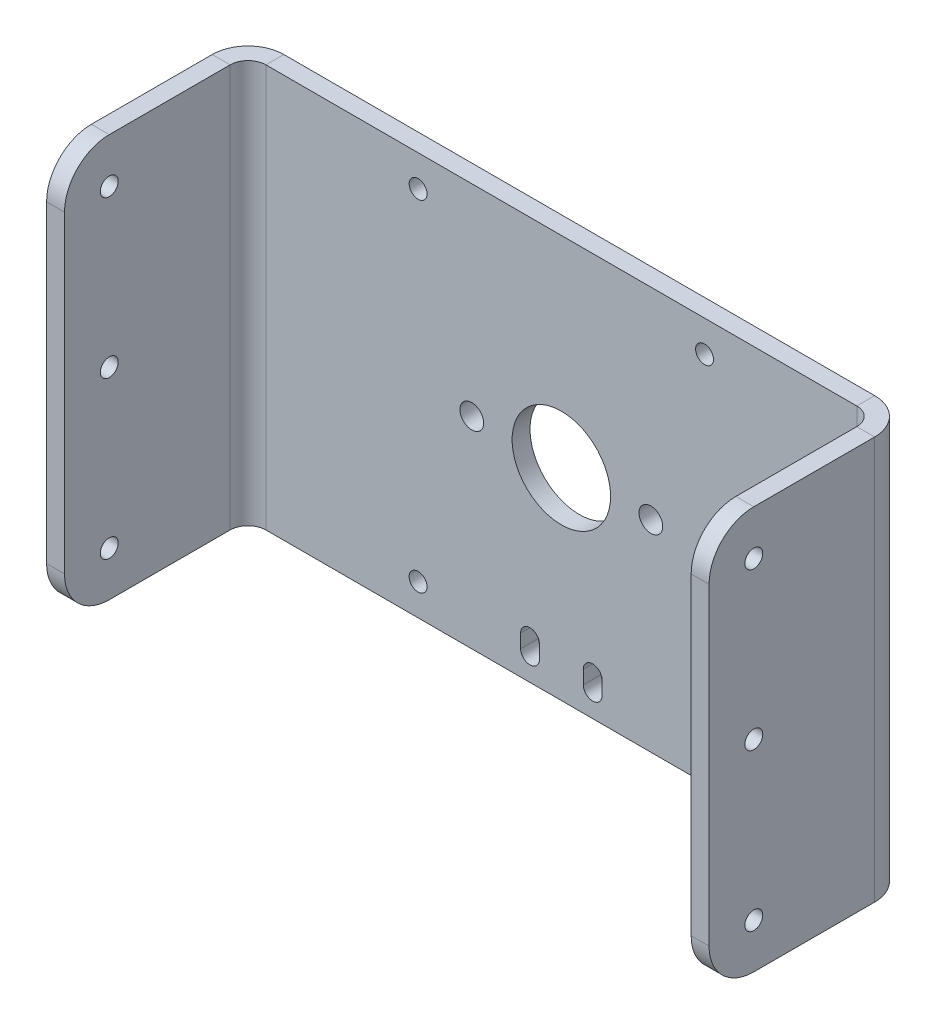
SolidWorks part; units mm, degrees
note: The reader was unsure of these and kept them because the rebuilt part matched: thickness of "Базовая кромка1", "Ребро-кромка1", "Листовой металл3", "Листовой металл4", "Листовой металл5", "Листовой металл7"; flange length of "Ребро-кромка1".
ref_plane "Спереди" through (0, 0, 0) normal (0, 0, 1) x (1, 0, 0)
ref_plane "Сверху" through (0, 0, 0) normal (0, 1, 0) x (1, 0, 0)
ref_plane "Справа" through (0, 0, 0) normal (1, 0, 0) x (0, 0, -1)
sketch "Эскиз1" plane through (0, 0, 0) normal (0, 0, 1) x (1, 0, 0)
  line L1 (-74, -45) -> (74, -45)
  line L2 (-74, -45) -> (-74, 45)
  line L3 (-74, 45) -> (74, 45)
  line L4 (74, -45) -> (74, 45)
  line L5 (-74, -45) -> (74, 45) construction
  line L6 (-74, 45) -> (74, -45) construction
  line L13 (-7, -36.5) -> (-7, -39.5) construction
  line L14 (-4.9, -36.5) -> (-4.9, -39.5)
  line L15 (-9.1, -36.5) -> (-9.1, -39.5)
  line L16 (7, -36.5) -> (7, -39.5) construction
  line L17 (9.1, -36.5) -> (9.1, -39.5)
  line L18 (4.9, -36.5) -> (4.9, -39.5)
  circle A0 centre (0, 0) radius 11
  circle A1 centre (20, 0) radius 2.65
  circle A2 centre (-20, 0) radius 2.65
  arc A12 (-4.9, -36.5) -> (-9.1, -36.5) centre (-7, -36.5) ccw
  arc A13 (-9.1, -39.5) -> (-4.9, -39.5) centre (-7, -39.5) ccw
  arc A14 (9.1, -36.5) -> (4.9, -36.5) centre (7, -36.5) ccw
  arc A15 (4.9, -39.5) -> (9.1, -39.5) centre (7, -39.5) ccw
  point P0 (0, 0)
  point P31 (-7, -38)
  point P36 (7, -38)
  dimension "D3" = 22
  dimension "D4" = 5.3
  dimension "D13" = 2.1
  dimension "D1" = 90
  dimension "D2" = 148
  dimension "D5" = 20
  dimension "D6" = 20
  dimension "D14" = 14
  dimension "D15" = 7
  dimension "D16" = 7
  dimension "D17" = 3
base flange "Базовая кромка1" sketch "Эскиз1" thickness 4 reverse thickness direction no parameters "D1"=0.7366
edge flange "Ребро-кромка1" sketch "Эскиз10" flange profiles "Эскиз10", "Эскиз11" flange angle 90 flange length 45 flange position material inside bend radius 4 thickness 4 relief rectangular parameters "D6"=10, "D8"=1
sketch "Эскиз10" plane through (-74, 0, 0) normal (-1, 0, 0) x (0, -1, 0)
  line L2 (-45, 0) -> (-45, 41)
  line L3 (-45, 41) -> (45, 41)
  line L4 (45, 41) -> (45, 0)
  line L7 (-45, 0) -> (45, 0) construction
  line L8 (-45, 0) -> (45, 0)
sketch "Эскиз11" plane through (74, 0, 0) normal (1, 0, 0) x (0, 1, 0)
  line L0 (-45, 0) -> (45, 0) construction
  line L1 (-45, 0) -> (45, 0)
  line L2 (-45, 0) -> (-45, 41)
  line L3 (-45, 41) -> (45, 41)
  line L4 (45, 41) -> (45, 0)
bend "EdgeBend1" bend radius 4 bend angle 90 parameters "D5"=1
bend "EdgeBend2" bend radius 4 bend angle 90 parameters "D5"=2
sketch "Эскиз12" plane through (74, 0, 0) normal (1, 0, 0) x (0, 0, -1)
  line L11 (-41, 45) -> (-41, -45) construction
  circle A0 centre (-31, 35) radius 2
  circle A1 centre (-31, -35) radius 2
  circle A2 centre (-31, 0) radius 2
  dimension "D1" = 4
  dimension "D2" = 35
  dimension "D3" = 35
  dimension "D4" = 10
extrude "Вырез-Вытянуть1" cut sketch "Эскиз12" against normal through all normal cut yes
fillet "Скругление1" radius 10 4 edges at (-72, 45, 41) (-72, -45, 41) (72, -45, 41) (72, 45, 41)
sketch "Эскиз13" plane through (0, 0, 0) normal (0, 0, 1) x (1, 0, 0)
  line L1 (-32, -38) -> (32, -38) construction
  line L2 (-32, -38) -> (-32, 38) construction
  line L3 (-32, 38) -> (32, 38) construction
  line L4 (32, -38) -> (32, 38) construction
  line L5 (-32, -38) -> (32, 38) construction
  line L6 (-32, 38) -> (32, -38) construction
  circle A0 centre (-32, 38) radius 2
  circle A1 centre (32, 38) radius 2
  circle A2 centre (32, -38) radius 2
  circle A3 centre (-32, -38) radius 2
  point P0 (0, 0)
  dimension "D3" = 4
  dimension "D1" = 76
  dimension "D2" = 64
extrude "Вырез-Вытянуть2" cut sketch "Эскиз13" against normal through all normal cut yes
sketch "Сгиб-Линии1" [suppressed] plane through (0, 0, 0) normal (0, 1, 0) x (1, 0, 0)
sketch "Граничная рамка1" [suppressed] plane through (0, 0, 0) normal (0, 1, 0) x (1, 0, 0)
sheet metal parameters "Листовой металл3" thickness 4 parameters "D1"=0.7366, "D7"=3
flat pattern "Развертка3" [suppressed]
sketch "Сгиб-Линии2" plane through (0, 0, 0) normal (0, 1, 0) x (1, 0, 0)
sketch "Граничная рамка2" [suppressed] plane through (0, 0, 0) normal (0, 1, 0) x (1, 0, 0)
sheet metal parameters "Листовой металл4" thickness 4 parameters "D1"=0.7366, "D7"=3
flat pattern "Развертка3" [suppressed]
sketch "Сгиб-Линии2" plane through (0, 0, 0) normal (0, 1, 0) x (1, 0, 0)
sketch "Граничная рамка2" [suppressed] plane through (0, 0, 0) normal (0, 1, 0) x (1, 0, 0)
bend of the flat pattern "Плоское состояние-<EdgeBend1>1"
bend of the flat pattern "Плоское состояние-<EdgeBend2>1"
sheet metal parameters "Листовой металл5" thickness 4 parameters "D1"=0.7366, "D7"=3
flat pattern "Развертка3" [suppressed]
sketch "Сгиб-Линии2" plane through (0, 0, 0) normal (0, 1, 0) x (1, 0, 0)
sketch "Граничная рамка2" [suppressed] plane through (0, 0, 0) normal (0, 1, 0) x (1, 0, 0)
bend of the flat pattern "Плоское состояние-<EdgeBend1>1"
bend of the flat pattern "Плоское состояние-<EdgeBend2>1"
sheet metal parameters "Листовой металл7" thickness 4 parameters "D1"=0.7366, "D7"=3
flat pattern "Развертка3"
sketch "Сгиб-Линии2" plane through (0, 0, 0) normal (0, 0, 1) x (1, 0, 0)
  line L0 (70.7124, -45) -> (70.7124, 45) construction
  line L1 (-70.7124, 45) -> (-70.7124, -45) construction
  line L2 (70.7124, -45) -> (70.7124, 45) construction
  line L3 (-70.7124, 45) -> (-70.7124, -45) construction
sketch3d "Граничная рамка2" [suppressed]
  line L0 (-112.4248, -45, 0) -> (112.4248, -45, 0) construction
  line L1 (-112.4248, 45, 0) -> (112.4248, 45, 0) construction
  line L2 (-112.4248, -45, 0) -> (-112.4248, 45, 0) construction
  line L3 (112.4248, -45, 0) -> (112.4248, 45, 0) construction
bend of the flat pattern "Плоское состояние-<EdgeBend1>1"
bend of the flat pattern "Плоское состояние-<EdgeBend2>1"
